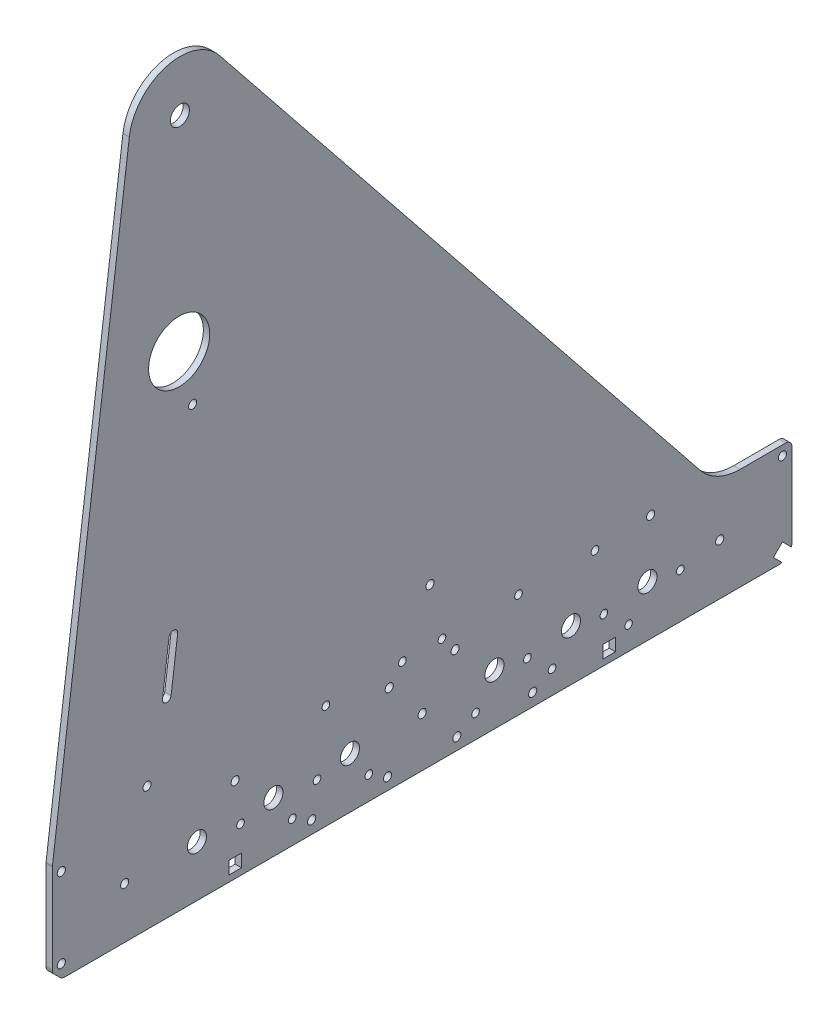
SolidWorks part; units mm, degrees
ref_plane "Front Plane" through (0, 0, 0) normal (0, 0, 1) x (1, 0, 0)
ref_plane "Top Plane" through (0, 0, 0) normal (0, 1, 0) x (1, 0, 0)
ref_plane "Right Plane" through (0, 0, 0) normal (1, 0, 0) x (0, 0, -1)
sketch "Sketch1" plane through (0, 0, 0) normal (1, 0, 0) x (0, 0, -1)
  line L0 (-184.15, -24.6062) -> (184.15, -24.6062)
  line L1 (184.15, -24.6062) -> (184.15, 26.1938)
  line L2 (184.15, 26.1938) -> (146.05, 26.1937)
  line L5 (-145.839, 321.5609) -> (-184.15, 26.1938)
  line L6 (-184.15, 26.1938) -> (-184.15, -24.6062)
  line L7 (-184.15, 350.0437) -> (184.15, 350.0437) construction
  line L9 (146.05, 26.1937) -> (-100.8314, 334.1803)
  arc A0 (-100.8314, 334.1803) -> (-145.839, 321.5609) centre (-120.65, 318.2937) ccw
  point P8 (0, -24.6062)
  dimension "D1" = 368.3
  dimension "D7" = 25.4
  dimension "D2" = 50.8
  dimension "D3" = 38.1
  dimension "D4" = 24.6062
  dimension "D5" = 374.65
  dimension "D6" = 304.8
  dimension "D8" = 342.9
extrude "Boss-Extrude1" add sketch "Sketch1" along normal blind 3.175
chamfer "Chamfer1" distance 4.7625 angle 45 2 edges at (1.5875, -24.6062, 184.15) (1.5875, -24.6062, -184.15)
fillet "Fillet1" radius 25.4 1 edges at (1.5875, 26.1937, -146.05)
fillet "Fillet2" radius 3.175 2 edges at (1.5875, 26.1938, 184.15) (1.5875, 26.1938, -184.15)
fillet "Fillet3" radius 3.175 4 edges at (1.5875, -19.8438, -184.15) (1.5875, -24.6062, -179.3875) (1.5875, -19.8437, 184.15) (1.5875, -24.6062, 179.3875)
sketch "Sketch30" [suppressed] plane through (3.175, 0, 0) normal (1, 0, 0) x (0, 0, -1)
  circle A8 centre (-89.211, 42.2593) radius 4.7625
  circle A9 centre (-25.1593, 30.6938) radius 2.032
  arc A10 (-51.7173, 35.4892) -> (-50.2741, 40.5715) centre (-25.1593, 30.6938) cw construction
  arc A11 (-54.7652, 42.3379) -> (-56.4665, 36.3468) centre (-25.1593, 30.6938) ccw
  arc A12 (-45.783, 38.8051) -> (-46.9681, 34.6317) centre (-25.1593, 30.6938) ccw
  arc A13 (-45.783, 38.8051) -> (-54.7652, 42.3379) centre (-50.2741, 40.5715) ccw
  arc A14 (-56.4665, 36.3468) -> (-46.9681, 34.6317) centre (-51.7173, 35.4892) ccw
  arc A15 (-34.9881, 56.6661) -> (-19.1131, 49.8125) centre (-41.7582, 19.1724) cw construction
  arc A16 (-17.6789, 51.753) -> (-34.5594, 59.0407) centre (-41.7582, 19.1724) ccw
  arc A17 (-20.5473, 47.8719) -> (-35.4169, 54.2915) centre (-41.7582, 19.1724) ccw
  arc A18 (-20.5473, 47.8719) -> (-17.6789, 51.753) centre (-19.1131, 49.8125) ccw
  arc A19 (-34.5594, 59.0407) -> (-35.4169, 54.2915) centre (-34.9881, 56.6661) ccw
  arc A20 (-19.1131, 49.8125) -> (-34.9881, 56.6661) centre (-41.7582, 19.1724) ccw construction
  circle A21 centre (94.6345, 23.8125) radius 2.032
  circle A22 centre (-56.6241, 64.5541) radius 2.032
  circle A23 centre (-43.9241, 64.5541) radius 2.032
  circle A24 centre (-56.6241, 64.5541) radius 1.905 construction
  circle A25 centre (-43.9241, 64.5541) radius 1.905 construction
  point P7 (-51.1204, 38.0658)
  point P19 (-26.6567, 54.1518)
  dimension "D2" = 9.652
  dimension "D4" = 4.064
  dimension "D1" = 4.064
  dimension ".375" = 9.525
  dimension "D3" = 4.826
extrude "Cut-Extrude9" [suppressed] cut sketch "Sketch30" against normal through all
sketch "Sketch16" plane through (3.175, 0, 0) normal (1, 0, 0) x (0, 0, -1)
  circle A0 centre (112.1746, 0.7937) radius 4.7625
  circle A1 centre (74.0746, 0.7937) radius 4.7625
  circle A2 centre (35.9746, 0.7937) radius 4.7625
  circle A3 centre (-35.9746, 0.7938) radius 4.7625
  circle A4 centre (-74.0746, 0.7938) radius 4.7625
  circle A5 centre (-112.1746, 0.7937) radius 4.7625
  dimension "D1" = 9.525
  dimension "D2" = 9.525
extrude "Cut-Extrude1" cut sketch "Sketch16" against normal up to next
sketch "Sketch25" plane through (3.175, 0, 0) normal (1, 0, 0) x (0, 0, -1)
  circle A0 centre (102.7672, -13.0003) radius 1.905 construction
  circle A1 centre (86.0486, 27.3622) radius 1.905 construction
  circle A2 centre (128.5804, -2.3081) radius 1.905 construction
  circle A3 centre (102.7672, -13.0003) radius 1.905
  circle A4 centre (86.0486, 27.3622) radius 1.905
  circle A5 centre (128.5804, -2.3081) radius 1.905
  circle A6 centre (64.6672, -13.0003) radius 1.905 construction
  circle A8 centre (-9.8486, 27.3622) radius 1.905 construction
  circle A10 centre (-47.9486, 27.3622) radius 1.905 construction
  circle A11 centre (-90.4804, -2.3081) radius 1.905 construction
  circle A12 centre (-64.6672, -13.0003) radius 1.905 construction
  circle A14 centre (-52.3804, -2.3081) radius 1.905 construction
  circle A15 centre (-26.5672, -13.0003) radius 1.905 construction
  circle A16 centre (9.8486, 27.3622) radius 1.905 construction
  circle A17 centre (26.5672, -13.0003) radius 1.905 construction
  circle A18 centre (47.9486, 27.3622) radius 1.905 construction
  circle A19 centre (52.3804, -2.3081) radius 1.905 construction
  circle A20 centre (90.4804, -2.3081) radius 1.905 construction
  circle A21 centre (-9.8486, 27.3622) radius 1.905
  circle A23 centre (-47.9486, 27.3622) radius 1.905
  circle A24 centre (-90.4804, -2.3081) radius 1.905
  circle A25 centre (-64.6672, -13.0003) radius 1.905
  circle A27 centre (-52.3804, -2.3081) radius 1.905
  circle A28 centre (-26.5672, -13.0003) radius 1.905
  circle A29 centre (9.8486, 27.3622) radius 1.905
  circle A30 centre (26.5672, -13.0003) radius 1.905
  circle A31 centre (47.9486, 27.3622) radius 1.905
  circle A32 centre (64.6672, -13.0003) radius 1.905
  circle A33 centre (52.3804, -2.3081) radius 1.905
  circle A34 centre (90.4804, -2.3081) radius 1.905
extrude "Cut-Extrude4" cut sketch "Sketch25" against normal up to next
sketch "Sketch23" plane through (3.175, 0, 0) normal (1, 0, 0) x (0, 0, -1)
  point P0 (-55.0246, -18.3223)
  point P6 (-93.1246, 17.5943)
  point P9 (-17.2515, -18.6426)
  point P12 (-16.4124, 19.3854)
  point P15 (16.4124, 19.3854)
  point P18 (17.2515, -18.6426)
  point P21 (55.0246, -18.3223)
  point P35 (3.8736, 53.6853)
  point P38 (113.7728, 28.6594)
  point P41 (-137.0088, 37.226)
  point P44 (-179.705, 21.7487)
  point P47 (-179.705, -18.0026)
  point P50 (179.3875, 21.4312)
hole_wizard "#8 (0.16) Diameter Hole1" positions "Sketch23" profile "Sketch24" hole size "#8" standard "ANSI Inch" end condition up to next
sketch "Sketch24" plane through (3.175, -18.3223, 55.0246) normal (0, 1, 0) x (0, 0, -1)
  line L0 (0, 0) -> (0, 3.175)
  line L1 (0, 3.175) -> (2.032, 3.175)
  line L2 (2.032, 3.175) -> (2.032, 0)
  line L5 (2.032, 0) -> (0, 0)
  line L11 (0, -6.35) -> (0, 107.95) construction
  dimension "Thru Hole Dia." = 4.064
  dimension "Thru Hole Depth" = 3.175
sketch "Sketch22" plane through (3.175, 0, 0) normal (1, 0, 0) x (0, 0, -1)
  line L0 (-96.2996, -15.1473) -> (-89.9496, -15.1473) construction
  line L1 (-96.2996, -15.1473) -> (-89.9496, -15.1473)
  line L2 (-96.2996, -15.1473) -> (-96.2996, -21.4973)
  line L3 (-96.2996, -21.4973) -> (-89.9496, -21.4973)
  line L4 (-89.9496, -15.1473) -> (-89.9496, -21.4973)
  line L5 (-96.2996, -15.1473) -> (-89.9496, -21.4973) construction
  line L6 (-96.2996, -21.4973) -> (-89.9496, -15.1473) construction
  line L7 (-89.9496, -15.1473) -> (-89.9496, -19.8734) construction
  line L77 (179.3875, -24.6062) -> (183.8776, -20.1161)
  line L78 (179.3875, -24.6062) -> (174.8974, -20.1161)
  line L79 (183.8776, -20.1161) -> (179.3875, -15.626)
  line L80 (174.8974, -20.1161) -> (179.3875, -15.626)
  line L81 (180.3174, -23.6763) -> (183.2201, -20.7737) construction
  line L82 (-178.0724, -24.6062) -> (178.0724, -24.6062) construction
  line L84 (89.9496, -21.4973) -> (96.2996, -21.4973)
  line L85 (89.9496, -21.4973) -> (89.9496, -15.1473)
  line L86 (89.9496, -15.1473) -> (96.2996, -15.1473)
  line L87 (96.2996, -21.4973) -> (96.2996, -15.1473)
  line L88 (89.9496, -21.4973) -> (96.2996, -15.1473) construction
  line L89 (89.9496, -15.1473) -> (96.2996, -21.4973) construction
  point P0 (-93.1246, -18.3223)
  point P19 (93.1246, -18.3223)
  dimension "D1" = 6.35
  dimension "D2" = 6.35
extrude "Cut-Extrude3" cut sketch "Sketch22" against normal up to next
sketch "Sketch21" plane through (3.175, 0, 0) normal (1, 0, 0) x (0, 0, -1)
  circle A0 centre (-148.1579, 0.7937) radius 2.032
  circle A2 centre (0, 0) radius 2.032
  circle A3 centre (148.1579, 0.7938) radius 2.032
  dimension "D1" = 4.064
extrude "Cut-Extrude2" cut sketch "Sketch21" against normal up to next
sketch "Sketch26" plane through (3.175, 0, 0) normal (1, 0, 0) x (0, 0, -1)
  line L0 (-145.839, 321.5609) -> (-184.1236, 26.3971) construction
  line L1 (-178.0724, -24.6062) -> (178.0724, -24.6062) construction
  circle A0 centre (-121.0218, 216.6937) radius 15.24
  dimension "D1" = 30.48
  dimension "D2" = 38.1
  dimension "D3" = 241.3
extrude "Cut-Extrude5" cut sketch "Sketch26" against normal through all
sketch "Sketch27" plane through (3.175, 0, 0) normal (1, 0, 0) x (0, 0, -1)
  circle A0 centre (-120.65, 318.2937) radius 4.7625
  dimension "D1" = 9.525
extrude "Cut-Extrude6" cut sketch "Sketch27" against normal through all
sketch "Sketch28" plane through (3.175, 0, 0) normal (1, 0, 0) x (0, 0, -1)
  line L0 (-120.65, 318.2937) -> (-103.5612, 277.2599) construction
  line L1 (-103.5612, 277.2599) -> (-86.3654, 258.566) construction
  line L2 (-86.3654, 258.566) -> (-90.1612, 246.4465) construction
  line L3 (-90.1612, 246.4465) -> (-93.9569, 234.327) construction
  line L4 (-145.839, 321.5609) -> (-184.1236, 26.3971) construction
  circle A0 centre (-93.9569, 234.327) radius 2.032
  circle A1 centre (-90.1612, 246.4465) radius 2.032
  circle A2 centre (-86.3654, 258.566) radius 2.0955
  circle A3 centre (-103.5612, 277.2599) radius 2.032
  dimension "D4" = 4.064
  dimension "D5" = 4.191
  dimension "D6" = 4.064
  dimension "D1" = 25.4
  dimension "D2" = 44.45
  dimension "D3" = 12.7
  dimension "D7" = 30
  dimension "D8" = 120
  dimension "D9" = 160
extrude "Cut-Extrude7" [suppressed] cut sketch "Sketch28" against normal through all
sketch "Sketch29" [suppressed] plane through (3.175, 0, 0) normal (1, 0, 0) x (0, 0, -1)
  line L0 (-145.839, 321.5609) -> (-184.1236, 26.3971) construction
  line L1 (-67.1375, 233.9197) -> (-74.4276, 216.3198) construction
  line L2 (-65.2602, 233.1421) -> (-72.5503, 215.5422)
  line L3 (-69.0148, 234.6973) -> (-76.305, 217.0974)
  line L4 (-67.1375, 233.9197) -> (-67.1375, 253.7354) construction
  circle A0 centre (-136.9875, 291.0697) radius 2.032
  circle A2 centre (-120.65, 318.2937) radius 4.7625 construction
  arc A4 (-65.2602, 233.1421) -> (-69.0148, 234.6973) centre (-67.1375, 233.9197) ccw
  arc A5 (-76.305, 217.0974) -> (-72.5503, 215.5422) centre (-74.4276, 216.3198) ccw
  point P8 (-70.7826, 225.1198)
  dimension "D1" = 31.75
  dimension "D2" = 4.064
  dimension "D3" = 69.85
  dimension "D4" = 12.7
  dimension "D5" = 57.15
  dimension "D6" = 19.05
  dimension "D7" = 22.5
extrude "Cut-Extrude8" [suppressed] cut sketch "Sketch29" against normal through all
sketch "Sketch31" plane through (0, 0, 0) normal (-1, 0, 0) x (0, 0, 1)
  circle A1 centre (114.3, 190.5) radius 2.032
  dimension "D1" = 114.3
  dimension "D6" = 4.064
  dimension "D2" = 190.5
extrude "Cut-Extrude10" cut sketch "Sketch31" against normal through all
sketch "Sketch34" plane through (0, 0, 0) normal (-1, 0, 0) x (0, 0, 1)
  line L3 (123.9045, 95.7355) -> (127.1716, 70.5465) construction
  line L4 (126.0455, 96.0132) -> (129.3127, 70.8242)
  line L5 (121.7634, 95.4578) -> (125.0306, 70.2688)
  line L6 (145.839, 321.5609) -> (184.1236, 26.3971) construction
  arc A2 (126.0455, 96.0132) -> (121.7634, 95.4578) centre (123.9045, 95.7355) ccw
  arc A3 (125.0306, 70.2688) -> (129.3127, 70.8242) centre (127.1716, 70.5465) ccw
  point P9 (125.538, 83.141)
  point P18 (114.3, 190.5)
  dimension "D8" = 4.318
  dimension "D6" = 50.8
  dimension "D7" = 25.4
  dimension "D9" = 95.25
extrude "Cut-Extrude12" cut sketch "Sketch34" against normal through all
sketch "Sketch37" [suppressed] plane through (3.175, 0, 0) normal (1, 0, 0) x (0, 0, -1)
  circle A0 centre (5.3975, 80.645) radius 2.032
  circle A8 centre (0, 0) radius 2.032 construction
  dimension "D1" = 4.064
  dimension "D2" = 5.3975
  dimension "D3" = 80.645
extrude "Cut-Extrude13" [suppressed] cut sketch "Sketch37" against normal through all
sketch "Sketch38" [suppressed] plane through (3.175, 0, 0) normal (1, 0, 0) x (0, 0, -1)
  line L0 (-184.15, 25.9887) -> (-184.15, -18.5286) construction
  line L1 (-178.0724, -24.6062) -> (178.0724, -24.6062) construction
  circle A0 centre (-152.4, 42.0688) radius 4.7625
  dimension "D1" = 31.75
  dimension "D3" = 9.525
  dimension "D2" = 66.675
extrude "Cut-Extrude14" [suppressed] cut sketch "Sketch38" against normal through all
